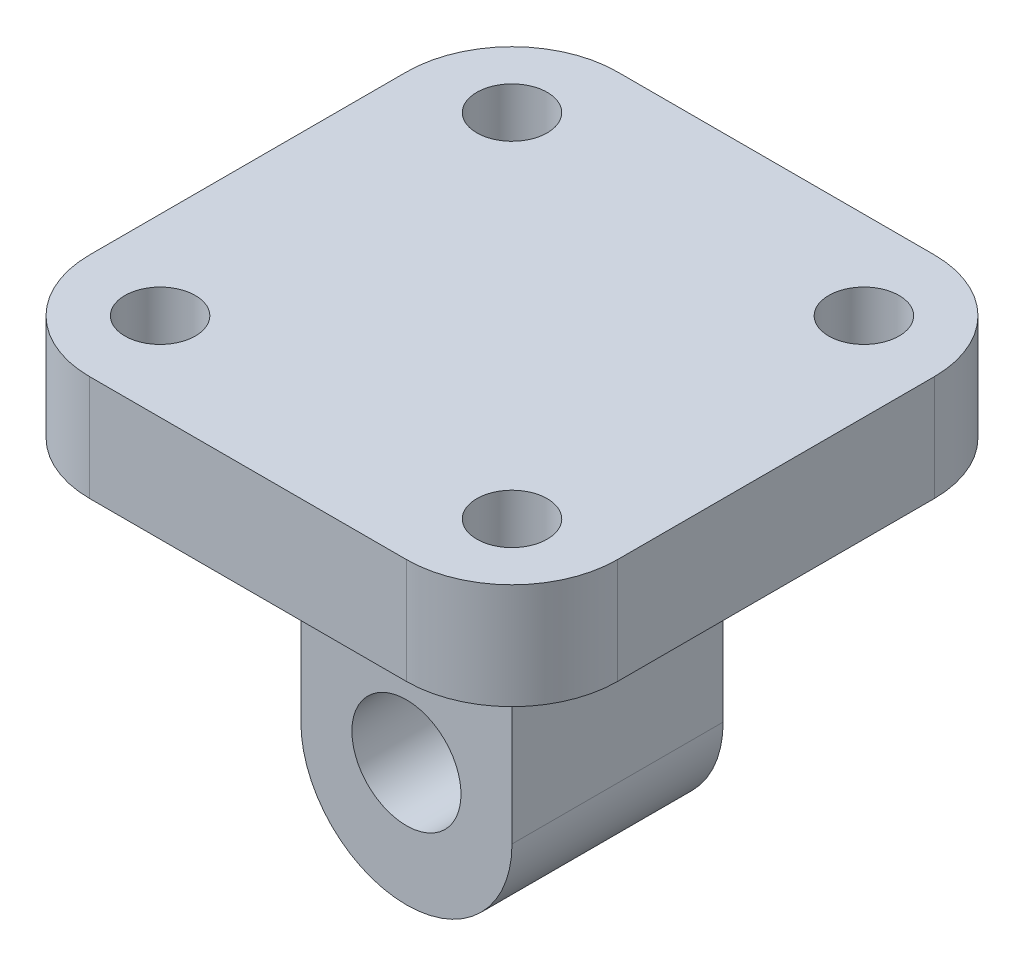
SolidWorks part; units mm, degrees
ref_plane "Front" through (0, 0, 0) normal (0, 0, 1) x (1, 0, 0)
ref_plane "Top" through (0, 0, 0) normal (0, 1, 0) x (1, 0, 0)
ref_plane "Right" through (0, 0, 0) normal (1, 0, 0) x (0, 0, -1)
sketch "Sketch1" plane through (0, 0, 0) normal (0, 1, 0) x (1, 0, 0)
  line L1 (0, 0) -> (15, 0)
  line L2 (0, 0) -> (0, -15)
  line L3 (0, -15) -> (15, -15)
  line L4 (15, 0) -> (15, -15)
  dimension "D1" = 15
  dimension "D2" = 15
extrude "Boss-Extrude1" add sketch "Sketch1" along normal blind 3
sketch "Sketch3" plane through (0, 3, 0) normal (0, 1, 0) x (1, 0, 0)
  line L0 (0, -15) -> (15, -15) construction
  line L1 (0, 0) -> (0, -15) construction
  circle A0 centre (2.5, -12.5) radius 1
  circle A1 centre (12.5, -12.5) radius 1
  circle A2 centre (12.5, -2.5) radius 1
  circle A3 centre (2.5, -2.5) radius 1
  dimension "D1" = 2
  dimension "D2" = 2.5
  dimension "D3" = 2.5
  dimension "D4" = 2
  dimension "D5" = 2
extrude "Cut-Extrude1" cut sketch "Sketch3" against normal through all
fillet "Fillet1" radius 3 4 edges at (15, 1.5, 15) (0, 1.5, 15) (15, 1.5, 0) (0, 1.5, 0)
sketch "Sketch4" plane through (0, 0, 0) normal (0, -1, 0) x (-1, 0, 0)
  line L0 (-3, -15) -> (-12, -15) construction
  line L1 (-10.5, -4.5) -> (-4.5, -4.5)
  line L2 (-10.5, -4.5) -> (-10.5, -10.5)
  line L3 (-10.5, -10.5) -> (-4.5, -10.5)
  line L4 (-4.5, -4.5) -> (-4.5, -10.5)
  line L5 (0, -3) -> (0, -12) construction
  dimension "D1" = 6
  dimension "D2" = 6
  dimension "D3" = 4.5
  dimension "D4" = 4.5
extrude "Boss-Extrude2" add sketch "Sketch4" along normal blind 10
sketch "Sketch5" plane through (0, 0, 4.5) normal (0, 0, -1) x (-1, 0, 0)
  line L0 (-10.5, -10) -> (-4.5, -10) construction
  line L3 (-4.5, -10) -> (-4.5, 0) construction
  circle A0 centre (-7.5, -6.5) radius 1.55
  dimension "D1" = 3.5
  dimension "D2" = 3.1
  dimension "D3" = 3
extrude "Cut-Extrude2" cut sketch "Sketch5" against normal through all
fillet "Fillet2" radius 3 2 edges at (10.5, -10, 7.5) (4.5, -10, 7.5)
fillet "Fillet3" radius 2 4 edges at (4.5, 0, 7.5) (7.5, 0, 10.5) (10.5, 0, 7.5) (7.5, 0, 4.5)
